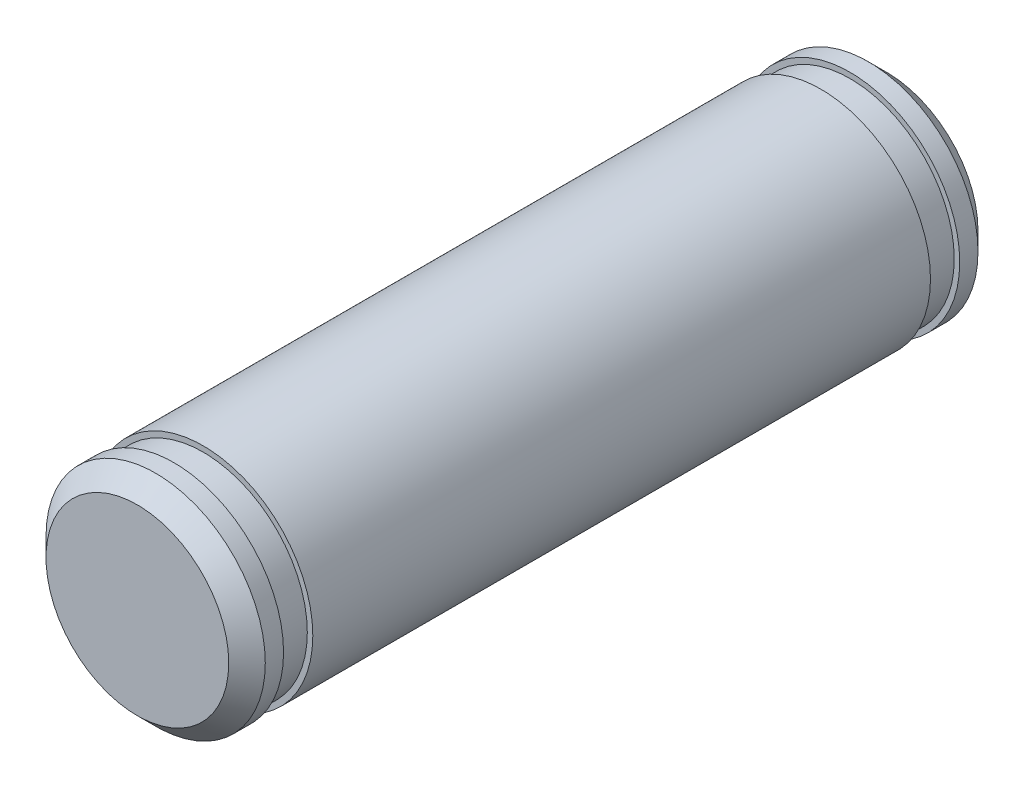
SolidWorks part; units mm, degrees
material "Stop 1060"
ref_plane "Płaszczyzna przednia" through (0, 0, 0) normal (0, 0, 1) x (1, 0, 0)
ref_plane "Płaszczyzna górna" through (0, 0, 0) normal (0, 1, 0) x (1, 0, 0)
ref_plane "Płaszczyzna prawa" through (0, 0, 0) normal (1, 0, 0) x (0, 0, -1)
sketch "Szkic1" plane through (0, 0, 0) normal (0, 0, 1) x (1, 0, 0)
  circle A0 centre (0, 0) radius 3
  dimension "D1" = 6
extrude "Dodanie-wyciągnięcie1" add sketch "Szkic1" along normal blind 20.5
sketch "Szkic2" plane through (0, 0, 20.5) normal (0, 0, 1) x (1, 0, 0)
  circle A0 centre (0, 0) radius 3
  circle A1 centre (0, 0) radius 2.85
  dimension "D1" = 6
  dimension "D2" = 5.7
extrude "Wytnij-wyciągnięcie1" cut sketch "Szkic2" against normal blind 0.8 from offset 1 offset against normal yes
extrude "Wytnij-wyciągnięcie2" cut sketch "Szkic2<2>" along normal blind 0.8 from offset 19.5 offset against normal yes
sketch "Szkic2<2>" plane through (0, 0, 20.5) normal (0, 0, 1) x (1, 0, 0) same geometry as "Szkic2"
chamfer "Sfazowanie1" distance 0.5 angle 45 2 edges at (3, 0, 0) (3, 0, 20.5)
